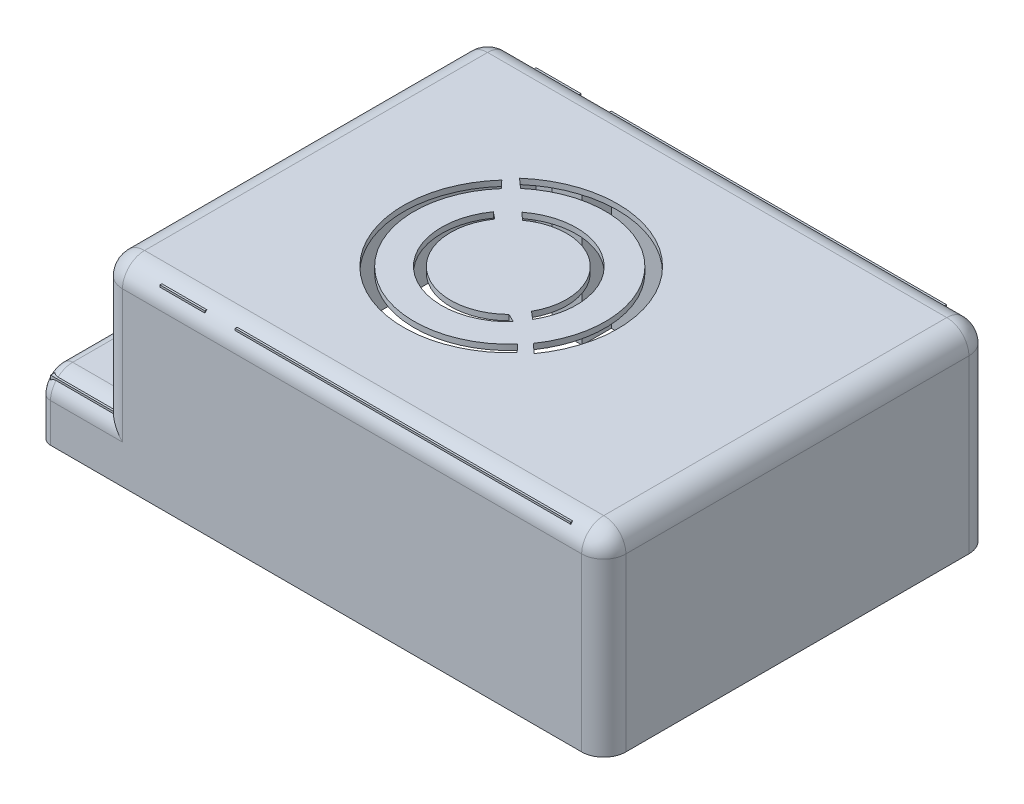
SolidWorks part; units mm, degrees
ref_plane "Front Plane" through (0, 0, 0) normal (0, 0, 1) x (1, 0, 0)
ref_plane "Top Plane" through (0, 0, 0) normal (0, 1, 0) x (1, 0, 0)
ref_plane "Right Plane" through (0, 0, 0) normal (1, 0, 0) x (0, 0, -1)
sketch "Sketch1" plane through (0, 0, 0) normal (0, 1, 0) x (1, 0, 0)
  line L0 (0, 0) -> (102, 0)
  line L1 (102, 0) -> (102, 70)
  line L2 (102, 70) -> (0, 70)
  line L3 (0, 70) -> (0, 0)
extrude "Boss-Extrude3" add sketch "Sketch1" along normal blind 35
sketch "Sketch4" plane through (0, 0, 0) normal (0, 1, 0) x (1, 0, 0)
  line L0 (0, 0) -> (11, 0)
  line L1 (0, 0) -> (102, 0) construction
  line L2 (11, 0) -> (11, 70)
  line L3 (102, 70) -> (0, 70) construction
  line L4 (11, 70) -> (0, 70)
  line L5 (0, 70) -> (0, 0)
extrude "Cut-Extrude1" cut sketch "Sketch4" along normal through all
sketch "Sketch5" plane through (0, 0, 0) normal (0, 1, 0) x (1, 0, 0)
  line L0 (0, 0) -> (11, 0)
  line L1 (11, 0) -> (11, 70)
  line L2 (11, 70) -> (0, 70)
  line L3 (0, 70) -> (0, 0)
extrude "Boss-Extrude4" add sketch "Sketch5" along normal blind 11
sketch "Sketch6" plane through (0, 0, 0) normal (0, 1, 0) x (1, 0, 0)
  line L0 (1, 1) -> (1, 69)
  line L1 (1, 69) -> (20.7743, 69)
  line L2 (20.7743, 69) -> (20.7743, 1)
  line L3 (20.7743, 1) -> (1, 1)
extrude "Cut-Extrude2" cut sketch "Sketch6" along normal blind 10
sketch "Sketch7" plane through (0, 0, 0) normal (0, 1, 0) x (1, 0, 0)
  line L0 (20.7743, 1) -> (100.4129, 1)
  line L1 (100.4129, 1) -> (100.4129, 69)
  line L2 (100.4129, 69) -> (20.7743, 69)
  line L3 (20.7743, 69) -> (20.7743, 1)
extrude "Cut-Extrude3" cut sketch "Sketch7" along normal blind 34
sketch "Sketch8" plane through (0, 10, 0) normal (0, -1, 0) x (-1, 0, 0)
  circle A0 centre (-6.858, 57) radius 3
  circle A1 centre (-6.858, 43) radius 3
  circle A2 centre (-6.858, 29) radius 3
  circle A3 centre (-6.858, 15) radius 3
extrude "Cut-Extrude4" cut sketch "Sketch8" against normal through all and the other way through all
sketch "Sketch9" plane through (0, 0, 0) normal (0, 1, 0) x (1, 0, 0)
  line L0 (1, 1) -> (100.4129, 1) construction
  line L1 (100.4129, 1) -> (95.0271, 1)
  line L2 (100.4129, 1) -> (100.4129, 6.9391)
  line L3 (100.4129, 6.9391) -> (95.0271, 6.9391)
  line L4 (95.0271, 1) -> (95.0271, 6.9391)
  line L5 (34.3673, 1) -> (28.8957, 1)
  line L6 (34.3673, 1) -> (34.3673, 6.9391)
  line L7 (34.3673, 6.9391) -> (28.8957, 6.9391)
  line L8 (28.8957, 1) -> (28.8957, 6.9391)
  line L9 (100.4129, 69) -> (1, 69) construction
  line L10 (100.4129, 69) -> (94.9411, 69)
  line L11 (100.4129, 69) -> (100.4129, 63.718)
  line L12 (100.4129, 63.718) -> (94.9411, 63.718)
  line L13 (94.9411, 69) -> (94.9411, 63.718)
  line L14 (34.3673, 69) -> (28.8957, 69)
  line L15 (34.3673, 69) -> (34.3673, 63.718)
  line L16 (34.3673, 63.718) -> (28.8957, 63.718)
  line L17 (28.8957, 69) -> (28.8957, 63.718)
extrude "Boss-Extrude6" add sketch "Sketch9" along normal through all
sketch "Sketch10" plane through (0, 0, 0) normal (0, 1, 0) x (1, 0, 0)
  circle A0 centre (70, 54) radius 3
  circle A1 centre (30, 54) radius 3
  circle A2 centre (30, 14) radius 3
  circle A3 centre (70, 14) radius 3
extrude "Boss-Extrude7" add sketch "Sketch10" along normal through all
sketch "Sketch11" plane through (0, 0, 0) normal (0, 1, 0) x (1, 0, 0)
  circle A0 centre (70, 14) radius 3
  circle A1 centre (70, 54) radius 3
  circle A2 centre (30, 54) radius 3
  circle A3 centre (30, 14) radius 3
extrude "Cut-Extrude5" cut sketch "Sketch11" along normal blind 31
hole_wizard "CSK for #0 Flat Head Machine Screw (100)1" positions "Sketch12" profile "Sketch13" countersink size "#0" standard "ANSI Inch"
sketch "Sketch12" plane through (0, 0, 0) normal (0, -1, 0) x (-1, 0, 0)
  point P0 (-98.8447, 4.0293)
  point P2 (-96.9849, 66.6625)
  point P4 (-31.564, 4.0293)
  point P6 (-31.564, 66.3105)
  point P7 (-98.8447, 66.6625)
  point P9 (-98.8447, 4.0293)
sketch "Sketch13" plane through (98.8447, 0, -4.0293) normal (1, 0, 0) x (0, 0, -1)
  line L0 (0, 0) -> (0, 15.5342)
  line L1 (0, 15.5342) -> (0.889, 15)
  line L2 (0.889, 15) -> (0.889, 0.5222)
  line L3 (0.889, 0.5222) -> (1.5113, 0)
  line L5 (1.5113, 0) -> (0, 0)
  line L6 (-0.889, 0.5222) -> (-1.5113, 0) construction
  line L10 (0, 15.5342) -> (-0.889, 15) construction
  line L11 (0, -6.35) -> (0, 107.95) construction
  dimension "Hole Dia." = 1.778
  dimension "Hole Depth" = 15
  dimension "Near C'Sink Dia." = 3.0226
  dimension "Near C'Sink Angle" = 100
  dimension "Drill Angle" = 118
hole_wizard "CSK for M2 Flat Head Machine Screw2" positions "Sketch14" profile "Sketch15" countersink size "M2" standard "ANSI Metric"
sketch "Sketch14" plane through (0, 31, 0) normal (0, -1, 0) x (-1, 0, 0)
  point P3 (-30, 14)
  point P6 (-30, 54)
  point P9 (-70, 54)
  point P12 (-70, 14)
sketch "Sketch15" plane through (30, 31, -14) normal (1, 0, 0) x (0, 0, -1)
  line L0 (0, 0) -> (0, 3.921)
  line L1 (0, 3.921) -> (1.2, 3.2)
  line L2 (1.2, 3.2) -> (1.2, 1)
  line L3 (1.2, 1) -> (2.2, 0)
  line L5 (2.2, 0) -> (0, 0)
  line L6 (-1.2, 1) -> (-2.2, 0) construction
  line L10 (0, 3.921) -> (-1.2, 3.2) construction
  line L11 (0, -6.35) -> (0, 107.95) construction
  dimension "Hole Dia." = 2.4
  dimension "Hole Depth" = 3.2
  dimension "Near C'Sink Dia." = 4.4
  dimension "Near C'Sink Angle" = 90
  dimension "Drill Angle" = 118
sketch "Sketch16" plane through (0, 0, 0) normal (0, 1, 0) x (1, 0, 0)
  line L0 (64.6699, 24.5976) -> (66.3531, 23.0723)
  line L1 (39.2627, 47.689) -> (37.57, 49.2069)
  line L2 (64.6699, 21.6756) -> (63.3602, 23.0496)
  line L3 (37.57, 45.9334) -> (36.2603, 47.3074)
  line L4 (60.8567, 28.2809) -> (59.4901, 29.4537)
  line L5 (44.4154, 42.8719) -> (43.1172, 44.1126)
  line L6 (40.4475, 41.5787) -> (41.7348, 40.5646)
  line L7 (59.4901, 26.1772) -> (57.9401, 26.9267)
  arc A0 (37.57, 49.2069) -> (66.3531, 23.0723) centre (50.4651, 34.4915) cw
  arc A1 (36.2603, 47.3074) -> (64.6699, 21.6756) centre (50.4651, 34.4915) ccw
  arc A2 (64.6699, 24.5976) -> (39.2627, 47.689) centre (50.4651, 34.4915) ccw
  arc A3 (37.57, 45.9334) -> (63.3602, 23.0496) centre (50.4651, 34.4915) ccw
  arc A4 (60.8567, 28.2809) -> (43.1172, 44.1126) centre (50.4651, 34.4915) ccw
  arc A5 (40.4475, 41.5787) -> (59.4901, 26.1772) centre (50.4651, 34.4915) ccw
  arc A6 (59.4901, 29.4537) -> (44.4154, 42.8719) centre (50.4651, 34.4915) ccw
  arc A7 (41.7348, 40.5646) -> (57.9401, 26.9267) centre (50.4651, 34.4915) ccw
extrude "Cut-Extrude6" cut sketch "Sketch16" along normal through all
fillet "Fillet4" radius 4 10 edges at (102, 35, -35) (56.5, 35, -70) (11, 35, -35) (56.5, 35, 0) (102, 17.5, 0) (102, 17.5, -70) (5.5, 11, -70) (11, 23, 0) (11, 23, -70) (5.5, 11, 0)
fillet "Fillet5" radius 2 5 edges at (0, 3.5, -70) (0, 9.8284, -68.8284) (0, 11, -35) (0, 9.8284, -1.1716) (0, 3.5, 0)
fillet "Fillet6" radius 1 1 edges at (6.858, 11, -12)
fillet "Fillet8" radius 1 3 edges at (6.858, 11, -54) (6.858, 11, -40) (6.858, 11, -26)
